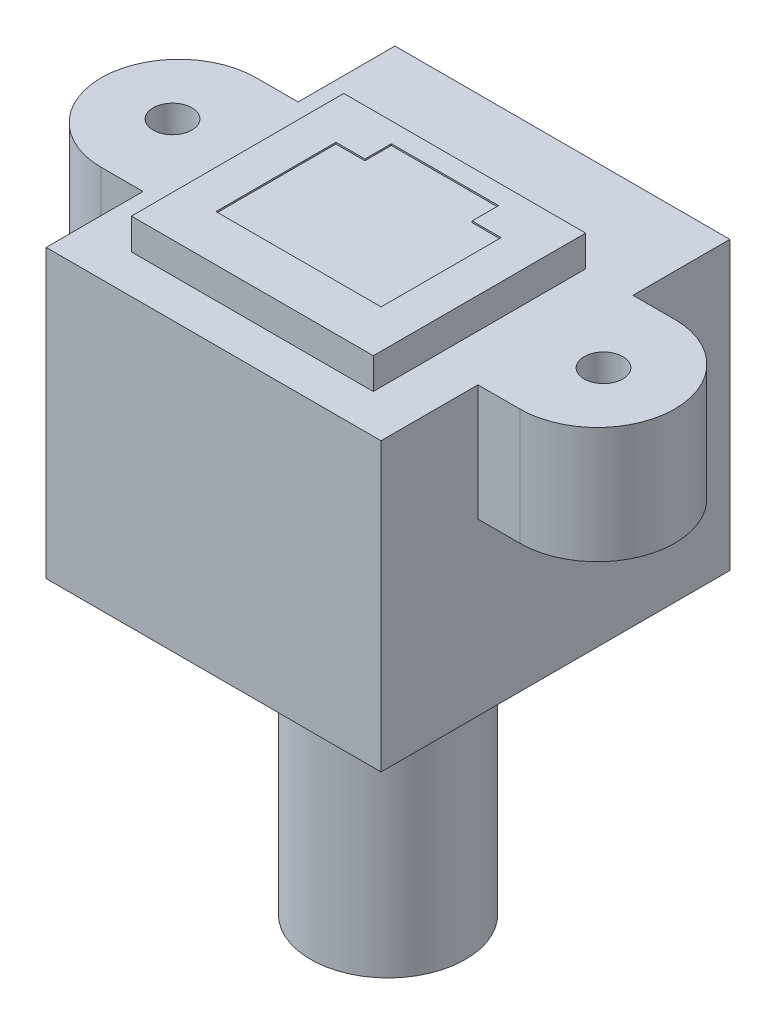
SolidWorks part; units mm, degrees
ref_plane "前视基准面" through (0, 0, 0) normal (0, 0, 1) x (1, 0, 0)
ref_plane "上视基准面" through (0, 0, 0) normal (0, 1, 0) x (1, 0, 0)
ref_plane "右视基准面" through (0, 0, 0) normal (1, 0, 0) x (0, 0, -1)
sketch "草图1" plane through (0, 0, 0) normal (0, 1, 0) x (1, 0, 0)
  line L1 (7.8, -6.85) -> (-7.8, -6.85)
  line L2 (7.8, -6.85) -> (7.8, 6.85)
  line L3 (7.8, 6.85) -> (-7.8, 6.85)
  line L4 (-7.8, -6.85) -> (-7.8, 6.85)
  line L5 (7.8, -6.85) -> (-7.8, 6.85) construction
  line L6 (7.8, 6.85) -> (-7.8, -6.85) construction
  point P0 (0, 0)
  dimension "D1" = 15.6
  dimension "D2" = 13.7
extrude "凸台-拉伸1" add sketch "草图1" along normal blind 2
sketch "草图3" plane through (0, 0, 0) normal (0, -1, 0) x (1, 0, 0)
  line L0 (0, 0) -> (0, 4.4279) construction
  line L1 (-10.8, 9.35) -> (10.8, 9.35)
  line L2 (-10.8, 9.35) -> (-10.8, 3.1)
  line L3 (-10.8, -13.15) -> (10.8, -13.15)
  line L4 (10.8, 9.35) -> (10.8, 3.1)
  line L5 (-7.8, 6.85) -> (7.8, 6.85) construction
  line L6 (-13.5, 3.1) -> (-10.8, 3.1)
  line L7 (-13.5, -6.9) -> (-10.8, -6.9)
  line L8 (13.5, 3.1) -> (10.8, 3.1)
  line L9 (-10.8, -6.9) -> (-10.8, -13.15)
  line L10 (10.8, -6.9) -> (13.5, -6.9)
  line L11 (10.8, -6.9) -> (10.8, -13.15)
  line L12 (-10.8, 9.35) -> (-10.8, -13.15) construction
  arc A0 (13.5, -6.9) -> (13.5, 3.1) centre (13.5, -1.9) ccw
  arc A1 (-13.5, 3.1) -> (-13.5, -6.9) centre (-13.5, -1.9) ccw
  point P10 (-10.8, -1.9)
  dimension "D4" = 27
  dimension "D5" = 10
  dimension "D1" = 21.6
  dimension "D2" = 22.5
  dimension "D3" = 2.5
extrude "凸台-拉伸2" add sketch "草图3" along normal blind 7.5
sketch "草图4" plane through (0, -7.5, 0) normal (0, -1, 0) x (1, 0, 0)
  line L1 (-10.8, 9.35) -> (10.8, 9.35)
  line L2 (-10.8, 9.35) -> (-10.8, -13.15)
  line L3 (-10.8, -13.15) -> (10.8, -13.15)
  line L4 (10.8, 9.35) -> (10.8, -13.15)
extrude "凸台-拉伸3" add sketch "草图4" along normal blind 15
chamfer "倒角1" distance 4 angle 45 4 edges at (0, -22.5, 9.35) (10.8, -22.5, -1.9) (0, -22.5, -13.15) (-10.8, -22.5, -1.9)
sketch "草图5" plane through (0, -22.5, 0) normal (0, -1, 0) x (1, 0, 0)
  line L0 (0, 5.35) -> (0, -9.15) construction
  line L1 (6.8, 5.35) -> (-6.8, 5.35) construction
  line L2 (-6.8, -9.15) -> (6.8, -9.15) construction
  line L3 (6.8, -1.9) -> (-6.8, -1.9) construction
  line L4 (6.8, -9.15) -> (6.8, 5.35) construction
  line L5 (-6.8, 5.35) -> (-6.8, -9.15) construction
  circle A0 centre (0, -1.9) radius 5
  dimension "D1" = 10
extrude "凸台-拉伸4" add sketch "草图5" along normal blind 15
sketch "草图6" plane through (0, 2, 0) normal (0, 1, 0) x (1, 0, 0)
  line L0 (0, 0) -> (0, 6.85) construction
  line L1 (5.3267, -3.8696) -> (-5.3267, -3.8696)
  line L2 (5.3267, -3.8696) -> (5.3267, 3.8696)
  line L3 (5.3267, 3.8696) -> (3.4587, 3.8696)
  line L4 (-5.3267, -3.8696) -> (-5.3267, 3.8696)
  line L5 (5.3267, -3.8696) -> (-5.3267, 3.8696) construction
  line L6 (5.3267, 3.8696) -> (-5.3267, -3.8696) construction
  line L8 (-3.4587, 3.8696) -> (-3.4587, 5.5752)
  line L9 (-3.4587, 5.5752) -> (3.4587, 5.5752)
  line L10 (3.4587, 3.8696) -> (3.4587, 5.5752)
  line L11 (7.8, 6.85) -> (-7.8, 6.85) construction
  line L12 (-3.4587, 3.8696) -> (-5.3267, 3.8696)
  point P0 (0, 0)
extrude "切除-拉伸1" cut sketch "草图6" against normal blind 0.1
hole_wizard "M3 螺纹孔1" positions "草图7" profile "草图8" tap size "M3" standard "GB" end condition up to next
sketch "草图7" plane through (0, 0, 0) normal (0, 1, 0) x (1, 0, 0)
  line L0 (0, 0) -> (0, 4.8642) construction
  arc A0 (-13.5, 6.9) -> (-13.5, -3.1) centre (-13.5, 1.9) ccw construction
  point P0 (13.9, 1.9)
  point P2 (-13.9, 1.9)
  point P19 (-18.5, 1.9)
  dimension "D1" = 27.8
sketch "草图8" plane through (13.9, 0, -1.9) normal (1, 0, 0) x (0, 0, 1)
  line L0 (0, 0) -> (0, 7.5)
  line L1 (0, 7.5) -> (1.25, 7.5)
  line L2 (1.25, 7.5) -> (1.25, 0)
  line L5 (1.25, 0) -> (0, 0)
  line L11 (0, -6.35) -> (0, 107.95) construction
  dimension "通孔螺纹孔钻头直径" = 2.5
  dimension "通孔螺纹孔钻头深度" = 7.5
cosmetic thread "孔螺蚊线1" parameters "D2"=3
cosmetic thread "孔螺蚊线2" parameters "D2"=3
other "连接点1" parameters "直径"=2, "端头长度"=3
ref_axis "基准轴1" through (0, -47.5, -1.9) along (0, 1, 0)
